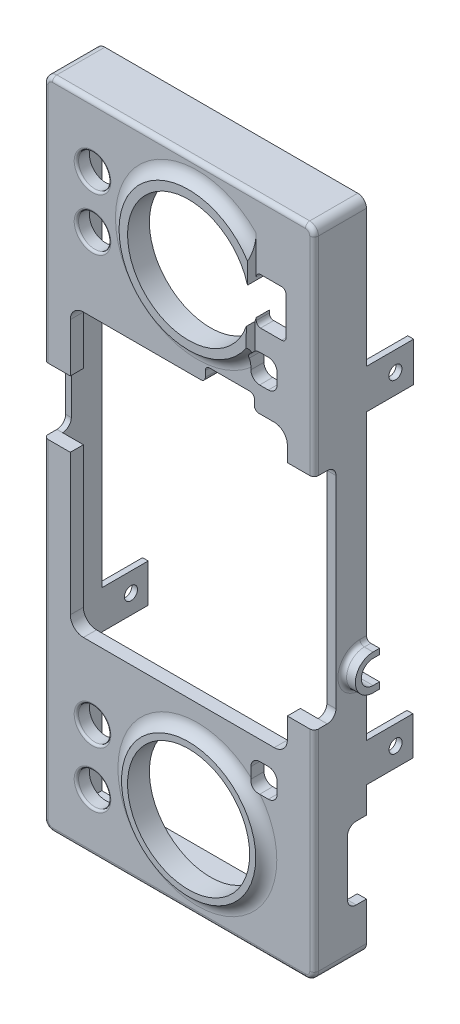
SolidWorks part; units mm, degrees
ref_plane "前视基准面" through (0, 0, 0) normal (0, 0, 1) x (1, 0, 0)
ref_plane "上视基准面" through (0, 0, 0) normal (0, 1, 0) x (1, 0, 0)
ref_plane "右视基准面" through (0, 0, 0) normal (1, 0, 0) x (0, 0, -1)
sketch "草图1" plane through (0, 0, 0) normal (0, 0, 1) x (1, 0, 0)
  line L1 (-42.3612, 43.872) -> (19.6264, 43.872)
  line L2 (-42.3612, 43.872) -> (-42.3612, -106.1368)
  line L3 (-42.3612, -106.1368) -> (19.6264, -106.1368)
  line L4 (19.6264, 43.872) -> (19.6264, -106.1368)
  line L5 (-41.0558, 41.6144) -> (17.5391, 41.6144)
  line L6 (-41.0558, 41.6144) -> (-41.0558, -104.1161)
  line L7 (-41.0558, -104.1161) -> (17.5391, -104.1161)
  line L8 (17.5391, 41.6144) -> (17.5391, -104.1161)
extrude "凸台-拉伸1" add sketch "草图1" along normal blind 9
sketch "草图3" plane through (0, 0, 9) normal (0, 0, 1) x (1, 0, 0)
  line L0 (6.3491, 19.543) -> (6.3491, 18.9478)
  line L1 (-5.3296, 0.8227) -> (-36.277, 0.8227)
  line L3 (5.9229, 0.8227) -> (5.9229, 4.1765)
  line L4 (-42.3612, 43.872) -> (-42.3612, -106.1368)
  line L5 (-42.3612, -106.1368) -> (19.6264, -106.1368)
  line L6 (19.6264, -106.1368) -> (19.6264, 43.872)
  line L7 (19.6264, 43.872) -> (-42.3612, 43.872)
  line L8 (-42.3612, 43.872) -> (-42.3612, -106.1368)
  line L9 (-42.3612, -106.1368) -> (19.6264, -106.1368)
  line L10 (19.6264, -106.1368) -> (19.6264, 43.872)
  line L11 (19.6264, 43.872) -> (-42.3612, 43.872)
  line L12 (5.9229, 4.1765) -> (-5.3296, 4.1765)
  line L13 (13.4811, 0.8227) -> (5.9229, 0.8227)
  line L14 (13.4811, 0.8227) -> (13.4811, -63.8006)
  line L15 (13.4811, -63.8006) -> (-36.277, -63.8006)
  line L16 (-36.277, 0.8227) -> (-36.277, -63.8006)
  line L18 (12.1838, 28.5875) -> (7.3491, 28.5875)
  line L19 (13.1838, 27.5875) -> (13.1838, 18.9478)
  line L20 (12.1838, 17.9478) -> (7.3491, 17.9478)
  line L21 (6.3491, 27.5875) -> (6.3491, 26.9603)
  line L30 (-5.3296, 0.8227) -> (-5.3296, 4.1765)
  line L31 (5.1257, 6.5448) -> (11.1257, 6.5448)
  line L32 (5.1257, 6.5448) -> (5.1257, 13.0448)
  line L33 (5.1257, 13.0448) -> (11.1257, 13.0448)
  line L34 (11.1257, 6.5448) -> (11.1257, 13.0448)
  line L35 (11.14, -68.2242) -> (5.14, -68.2242)
  line L36 (11.14, -68.2242) -> (11.14, -74.7242)
  line L37 (11.14, -74.7242) -> (5.14, -74.7242)
  line L38 (5.14, -68.2242) -> (5.14, -74.7242)
  arc A0 (6.3491, 26.9603) -> (6.3491, 19.543) centre (-7.1507, 23.2516) ccw
  circle A1 centre (-7.1507, -85.8433) radius 14
  circle A2 centre (-31.1873, 29.7935) radius 3.7013
  circle A3 centre (-31.1873, 17.7935) radius 3.7013
  circle A4 centre (-31.1873, -92.9392) radius 3.7013
  circle A5 centre (-31.1873, -80.0696) radius 3.7013
  arc A6 (7.3491, 17.9478) -> (6.3491, 18.9478) centre (7.3491, 18.9478) cw
  arc A7 (13.1838, 18.9478) -> (12.1838, 17.9478) centre (12.1838, 18.9478) cw
  arc A8 (12.1838, 28.5875) -> (13.1838, 27.5875) centre (12.1838, 27.5875) cw
  arc A9 (7.3491, 28.5875) -> (6.3491, 27.5875) centre (7.3491, 27.5875) ccw
  dimension "D4" = 28
  dimension "D5" = 6
  dimension "D18" = 1
  dimension "D2" = 28
  dimension "D3" = 6.5
  dimension "D6" = 6
  dimension "D10" = 6.5
  dimension "D13" = 12
  dimension "D1" = 0
extrude "凸台-拉伸2" add sketch "草图3" along normal blind 3
fillet "圆角1" radius 2 4 edges at (19.6264, 43.872, 6) (-42.3612, 43.872, 6) (19.6264, -106.1368, 6) (-42.3612, -106.1368, 6)
sketch "草图4" plane through (0, 0, 12) normal (0, 0, 1) x (1, 0, 0)
  line L0 (6.3491, 26.9603) -> (6.3491, 31.7494)
  line L1 (6.0489, 14.2946) -> (6.0707, 18.6479)
  circle A0 centre (-7.1507, 23.2516) radius 14 construction
  arc A1 (6.3491, 26.9603) -> (6.0707, 18.6479) centre (-7.1507, 23.2516) ccw
  circle A2 centre (-7.1507, -85.8433) radius 14 construction
  circle A3 centre (-7.1507, -85.8433) radius 14
  arc A4 (6.3491, 31.7494) -> (6.0489, 14.2946) centre (-7.1507, 23.2516) ccw
  circle A5 centre (-7.1507, -85.8433) radius 15.3905
extrude "凸台-拉伸3" add sketch "草图4" along normal blind 2
fillet "圆角2" radius 3 2 edges at (8.2397, -85.8433, 12) (-23.1001, 23.526, 12)
fillet "圆角3" radius 3 4 edges at (-36.277, -63.8006, 10.5) (13.4811, -63.8006, 10.5) (13.4811, 0.8227, 10.5) (-36.277, 0.8227, 10.5)
sketch "草图5" plane through (19.6264, 0, 0) normal (1, 0, 0) x (0, 0, -1)
  line L1 (-4.3521, -95.2894) -> (1.1577, -95.2894)
  line L2 (-4.3521, -95.2894) -> (-4.3521, -78.6542)
  line L3 (-4.3521, -78.6542) -> (1.1577, -78.6542)
  line L4 (1.1577, -95.2894) -> (1.1577, -78.6542)
extrude "切除-拉伸1" cut sketch "草图5" against normal blind 4
fillet "圆角5" radius 2 2 edges at (18.5827, -95.2894, 4.3521) (18.5827, -78.6542, 4.3521)
sketch "草图6" plane through (-42.3612, 0, 0) normal (-1, 0, 0) x (0, 0, 1)
  line L5 (2.752, -63.6815) -> (-10.6458, -63.6815)
  line L6 (2.752, -63.6815) -> (2.752, -72.826)
  line L7 (2.752, -72.826) -> (-10.6458, -72.826)
  line L8 (-10.6458, -63.6815) -> (-10.6458, -72.826)
  circle A1 centre (-6.6891, -68.2404) radius 1.5
extrude "凸台-拉伸4" add sketch "草图6" against normal up to surface (1.3054 mm away) up to face at (-41.0558, -31.2509, 4.5)
sketch "草图7" plane through (19.6264, 0, 0) normal (1, 0, 0) x (0, 0, -1)
  line L0 (0, -63.6815) -> (10.6458, -63.6815) construction
  line L5 (-3.0845, 1.3414) -> (10.8217, 1.3414)
  line L6 (-3.0845, 1.3414) -> (-3.0845, 10.5751)
  line L7 (-3.0845, 10.5751) -> (10.8217, 10.5751)
  line L8 (10.8217, 1.3414) -> (10.8217, 10.5751)
  line L9 (10.6458, -72.826) -> (-3.7002, -72.826)
  line L10 (10.6458, -72.826) -> (10.6458, -63.6815)
  line L11 (10.6458, -63.6815) -> (-3.7002, -63.6815)
  line L12 (-3.7002, -72.826) -> (-3.7002, -63.6815)
  circle A1 centre (6.6434, 5.9708) radius 1.5
  circle A2 centre (6.6891, -68.2404) radius 1.5 construction
  circle A3 centre (6.6891, -68.2404) radius 1.5
extrude "凸台-拉伸5" add sketch "草图7" against normal blind 1.35
fillet "圆角9" radius 2 8 edges at (5.1257, 13.0448, 11.4812) (5.1257, 6.5448, 10.5) (11.1257, 6.5448, 10.5) (11.1257, 13.0448, 10.5) (11.14, -68.2242, 10.5) (11.14, -74.7242, 10.5) (5.14, -68.2242, 10.5) (5.14, -74.7242, 10.7456)
sketch "草图8" plane through (19.6264, 0, 0) normal (1, 0, 0) x (0, 0, -1)
  line L0 (-1.4893, -47.9562) -> (6.2094, -47.9562) construction
  line L1 (-1.4893, -45.265) -> (6.2094, -45.265)
  line L2 (-1.4893, -50.6474) -> (6.2094, -50.6474)
  arc A0 (-1.4893, -45.265) -> (-1.4893, -50.6474) centre (-1.4893, -47.9562) ccw
  arc A1 (6.2094, -50.6474) -> (6.2094, -45.265) centre (6.2094, -47.9562) ccw
  point P2 (2.3601, -47.9562)
extrude "切除-拉伸2" cut sketch "草图8" against normal blind 3
sketch "草图9" plane through (19.6264, 0, 0) normal (1, 0, 0) x (0, 0, -1)
  line L0 (-12, -104.1368) -> (-12, 41.872) construction
  line L1 (-12, -56.0154) -> (-8.9948, -56.0154)
  line L2 (-12, -56.0154) -> (-12, -5.7111)
  line L3 (-12, -5.7111) -> (-8.9948, -5.7111)
  line L4 (-6.9948, -54.0154) -> (-6.9948, -7.7111)
  arc A0 (-8.9948, -5.7111) -> (-6.9948, -7.7111) centre (-8.9948, -7.7111) cw
  arc A1 (-8.9948, -56.0154) -> (-6.9948, -54.0154) centre (-8.9948, -54.0154) ccw
  dimension "D1" = 2
extrude "切除-拉伸3" cut sketch "草图9" against normal blind 10
sketch "草图10" plane through (-42.3612, 0, 0) normal (-1, 0, 0) x (0, 0, 1)
  line L0 (12, 41.872) -> (12, -104.1368) construction
  line L1 (12, -13.3772) -> (8.9948, -13.3772)
  line L2 (12, -13.3772) -> (12, -28.5301)
  line L3 (12, -28.5301) -> (8.9948, -28.5301)
  line L4 (6.9948, -15.3772) -> (6.9948, -26.5301)
  line L5 (6.9948, -7.7111) -> (6.9948, -54.0154) construction
  arc A0 (8.9948, -28.5301) -> (6.9948, -26.5301) centre (8.9948, -26.5301) cw
  arc A1 (8.9948, -13.3772) -> (6.9948, -15.3772) centre (8.9948, -15.3772) ccw
  point P10 (6.9948, -28.5301)
  dimension "D1" = 2
extrude "切除-拉伸4" cut sketch "草图10" against normal blind 10
fillet "圆角11" radius 1 5 edges at (19.6264, 18.0805, 12) (19.0406, 43.2862, 12) (-42.3612, 14.2474, 12) (-41.7755, 43.2862, 12) (-11.3674, 43.872, 12)
fillet "圆角13" radius 1 5 edges at (-42.3612, -66.3335, 12) (-41.7755, -105.551, 12) (19.6264, -80.0761, 12) (19.0406, -105.551, 12) (-11.3674, -106.1368, 12)
fillet "圆角14" radius 1 4 edges at (-5.3296, 4.1765, 10.5) (5.9229, 4.1765, 10.5) (-5.3296, 0.8227, 10.5) (5.9229, 0.8227, 10.5)
fillet "圆角15" radius 2 rebuild error yes
sketch "草图11" plane through (19.6264, 0, 0) normal (1, 0, 0) x (0, 0, -1)
  line L0 (-1.4893, -50.6474) -> (0, -50.6474) construction
  line L1 (-1.4893, -50.6474) -> (0, -50.6474)
  line L2 (0, -45.265) -> (-1.4893, -45.265) construction
  line L3 (0, -45.265) -> (-1.4893, -45.265)
  line L4 (0, -50.6474) -> (0, -52.1117)
  line L5 (0, -63.6815) -> (0, -50.6474) construction
  line L6 (0, -45.265) -> (0, -43.9957)
  line L7 (0, -45.265) -> (0, 1.3414) construction
  line L8 (0, -52.1117) -> (-1.4893, -52.1117)
  line L9 (0, -43.9957) -> (-1.4893, -43.9957)
  arc A0 (-1.4893, -45.265) -> (-1.4893, -50.6474) centre (-1.4893, -47.9562) ccw construction
  arc A1 (-1.4893, -45.265) -> (-1.4893, -50.6474) centre (-1.4893, -47.9562) ccw
  arc A2 (-1.4893, -52.1117) -> (-1.4893, -43.9957) centre (-1.4893, -48.0537) cw
extrude "凸台-拉伸6" add sketch "草图11" along normal blind 3
fillet "圆角16" radius 1 3 edges at (19.6264, -43.9957, 0.7446) (19.6264, -52.1117, 0.7446) (19.6264, -48.0537, 5.5472)
fillet "圆角17" radius 0.5 4 edges at (-27.486, -92.9392, 12) (-27.486, -80.0696, 12) (-27.486, 17.7935, 12) (-27.486, 29.7935, 12)
sketch "草图12" plane through (-42.3612, 0, 0) normal (-1, 0, 0) x (0, 0, 1)
  line L0 (-10.6458, -63.6815) -> (-10.6458, -72.826) construction
  line L1 (0, -72.826) -> (-10.6458, -72.826)
  line L2 (0, -72.826) -> (0, -72.6176)
  line L3 (0, -72.6176) -> (-10.6458, -72.6176)
  line L4 (-10.6458, -72.826) -> (-10.6458, -72.6176)
  line L5 (0, 41.872) -> (0, -63.6815) construction
  line L6 (-10.6458, -63.6815) -> (0, -63.6815)
  line L7 (-10.6458, -63.6815) -> (-10.6458, -63.8205)
  line L8 (-10.6458, -63.8205) -> (0, -63.8205)
  line L9 (0, -63.6815) -> (0, -63.8205)
  line L10 (-10.8217, 1.3414) -> (0, 1.3414)
  line L11 (-10.8217, 1.3414) -> (-10.8217, 1.4403)
  line L12 (-10.8217, 1.4403) -> (0, 1.4403)
  line L13 (0, 1.3414) -> (0, 1.4403)
  line L15 (0, 10.5751) -> (-10.9029, 10.5751)
  line L16 (0, 10.5751) -> (0, 10.4815)
  line L17 (0, 10.4815) -> (-10.9029, 10.4815)
  line L18 (-10.9029, 10.5751) -> (-10.9029, 10.4815)
extrude "切除-拉伸5" cut sketch "草图12" against normal through all both and the other way through all
